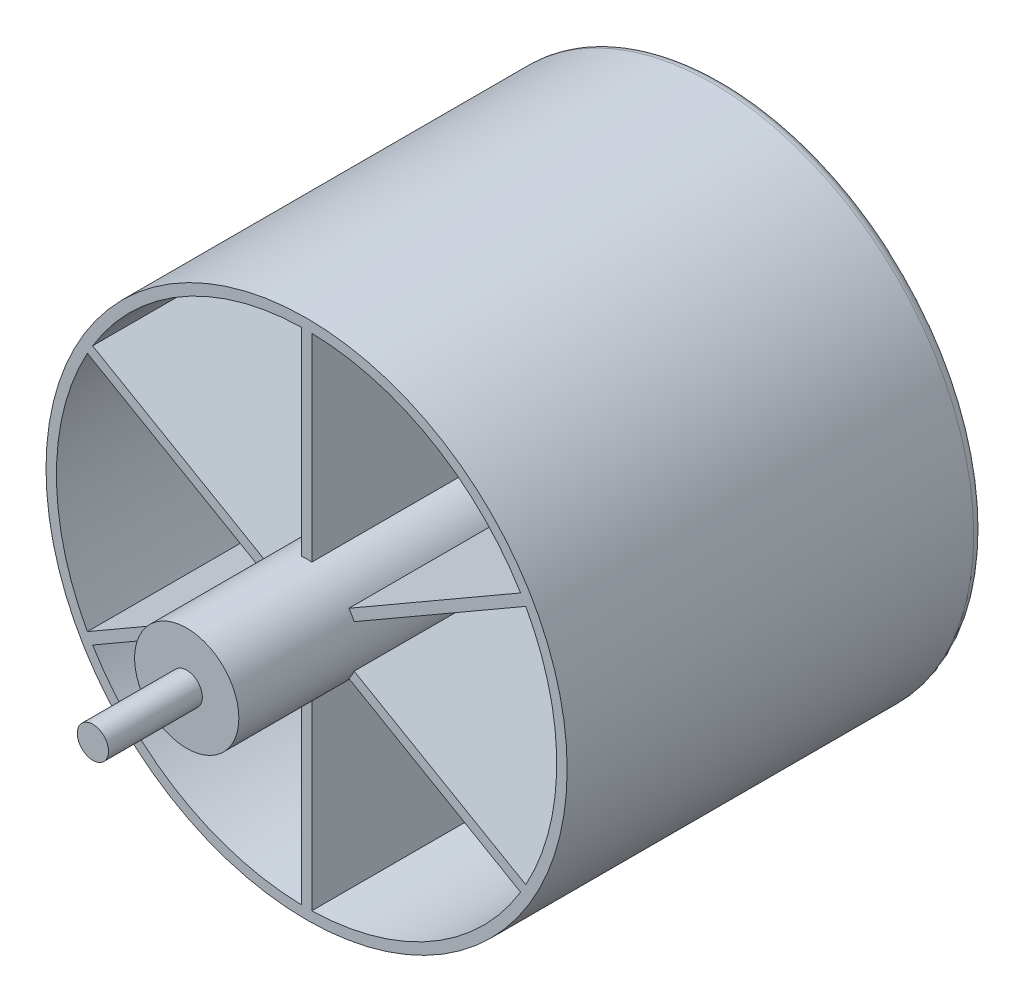
SolidWorks part; units mm, degrees
material "玻璃"
ref_plane "前视基准面" through (0, 0, 0) normal (0, 0, 1) x (1, 0, 0)
ref_plane "上视基准面" through (0, 0, 0) normal (0, 1, 0) x (1, 0, 0)
ref_plane "右视基准面" through (0, 0, 0) normal (1, 0, 0) x (0, 0, -1)
other "Configuration Table"
sketch "草图1" plane through (0, 0, 0) normal (0, 0, 1) x (1, 0, 0)
  circle A0 centre (0, 0) radius 50
  dimension "D1" = 100
extrude "凸台-拉伸1" add sketch "草图1" along normal blind 80
shell "抽壳1" thickness 2 removed face at (50, 0, 80)
sketch "草图2" plane through (0, 0, 2) normal (0, 0, 1) x (1, 0, 0)
  line L0 (0, -1000) -> (0, 49000) construction
  line L1 (-1, 9.9499) -> (-1, 47.9896)
  line L2 (1, 9.9499) -> (1, 47.9896)
  line L3 (8.1168, 5.841) -> (41.0602, 24.8608)
  line L4 (9.1168, 4.1089) -> (42.0602, 23.1288)
  line L5 (9.1168, -4.1089) -> (42.0602, -23.1288)
  line L6 (8.1168, -5.841) -> (41.0602, -24.8608)
  line L7 (1, -9.9499) -> (1, -47.9896)
  line L8 (-1, -9.9499) -> (-1, -47.9896)
  line L9 (-8.1168, -5.841) -> (-41.0602, -24.8608)
  line L10 (-9.1168, -4.1089) -> (-42.0602, -23.1288)
  line L11 (-9.1168, 4.1089) -> (-42.0602, 23.1288)
  line L12 (-8.1168, 5.841) -> (-41.0602, 24.8608)
  circle A0 centre (0, 0) radius 48 construction
  arc A1 (-41.0602, 24.8608) -> (-42.0602, 23.1288) centre (0, 0) ccw
  arc A2 (-9.1168, 4.1089) -> (-9.1168, -4.1089) centre (0, 0) ccw
  arc A3 (1, 47.9896) -> (-1, 47.9896) centre (0, 0) ccw
  arc A4 (42.0602, 23.1288) -> (41.0602, 24.8608) centre (0, 0) ccw
  arc A5 (41.0602, -24.8608) -> (42.0602, -23.1288) centre (0, 0) ccw
  arc A6 (-1, -47.9896) -> (1, -47.9896) centre (0, 0) ccw
  arc A7 (-42.0602, -23.1288) -> (-41.0602, -24.8608) centre (0, 0) ccw
  circle A8 centre (0, 0) radius 8
  arc A9 (-1, 9.9499) -> (-8.1168, 5.841) centre (0, 0) ccw
  arc A10 (8.1168, 5.841) -> (1, 9.9499) centre (0, 0) ccw
  arc A11 (9.1168, -4.1089) -> (9.1168, 4.1089) centre (0, 0) ccw
  arc A12 (-8.1168, -5.841) -> (-1, -9.9499) centre (0, 0) ccw
  arc A13 (1, -9.9499) -> (8.1168, -5.841) centre (0, 0) ccw
  point P32 (0, 0)
  dimension "D1" = 20
  dimension "D4" = 2
  dimension "D2" = 2
  dimension "D3" = 6
extrude "凸台-拉伸2" add sketch "草图2" along normal up to surface (78 mm away) up to face at (48, 0, 80)
sketch "草图3" plane through (0, 0, 2) normal (0, 0, 1) x (1, 0, 0)
  line L0 (0, -1000) -> (0, 49000) construction
  line L1 (0, 0) -> (-25000, 43301.2702) construction
  line L14 (-16.1245, 16.1245) -> (-26.0768, 26.0768)
  line L15 (-5.902, 22.0265) -> (-9.5448, 35.6216)
  line L16 (16.1245, 16.1245) -> (26.0768, 26.0768)
  line L17 (5.902, 22.0265) -> (9.5448, 35.6216)
  line L18 (22.0265, -5.902) -> (35.6216, -9.5448)
  line L19 (22.0265, 5.902) -> (35.6216, 9.5448)
  line L20 (5.902, -22.0265) -> (9.5448, -35.6216)
  line L21 (16.1245, -16.1245) -> (26.0768, -26.0768)
  line L22 (-16.1245, -16.1245) -> (-26.0768, -26.0768)
  line L23 (-5.902, -22.0265) -> (-9.5448, -35.6216)
  line L24 (-22.0265, 5.902) -> (-35.6216, 9.5448)
  line L25 (-22.0265, -5.902) -> (-35.6216, -9.5448)
  line L26 (0, 0) -> (-5.1764, 19.3185) construction
  line L27 (0, 0) -> (14.1421, 14.1421) construction
  arc A36 (-39.3492, 7.1859) -> (-39.3492, -7.1859) centre (0, 0) ccw
  arc A37 (-19.8287, 2.6124) -> (-19.8287, -2.6124) centre (0, 0) ccw
  arc A38 (-7.652, 18.4783) -> (-12.1767, 15.8659) centre (0, 0) ccw
  arc A39 (-13.4514, 37.6704) -> (-25.8978, 30.4845) centre (0, 0) ccw
  arc A40 (25.8978, 30.4845) -> (13.4514, 37.6704) centre (0, 0) ccw
  arc A41 (12.1767, 15.8659) -> (7.652, 18.4783) centre (0, 0) ccw
  arc A42 (19.8287, -2.6124) -> (19.8287, 2.6124) centre (0, 0) ccw
  arc A43 (39.3492, -7.1859) -> (39.3492, 7.1859) centre (0, 0) ccw
  arc A44 (7.652, -18.4783) -> (12.1767, -15.8659) centre (0, 0) ccw
  arc A45 (13.4514, -37.6704) -> (25.8978, -30.4845) centre (0, 0) ccw
  arc A46 (-25.8978, -30.4845) -> (-13.4514, -37.6704) centre (0, 0) ccw
  arc A47 (-12.1767, -15.8659) -> (-7.652, -18.4783) centre (0, 0) ccw
  arc A48 (-22.0265, -5.902) -> (-19.8287, -2.6124) centre (-22.803, -3.0042) ccw
  arc A49 (-22.0265, 5.902) -> (-19.8287, 2.6124) centre (-22.803, 3.0042) cw
  arc A50 (-35.6216, 9.5448) -> (-39.3492, 7.1859) centre (-36.398, 6.647) ccw
  arc A51 (-35.6216, -9.5448) -> (-39.3492, -7.1859) centre (-36.398, -6.647) cw
  arc A52 (-5.902, -22.0265) -> (-7.652, -18.4783) centre (-8.7998, -21.25) ccw
  arc A53 (-16.1245, -16.1245) -> (-12.1767, -15.8659) centre (-14.0032, -18.2458) cw
  arc A54 (-26.0768, -26.0768) -> (-25.8978, -30.4845) centre (-23.9555, -28.1981) ccw
  arc A55 (-9.5448, -35.6216) -> (-13.4514, -37.6704) centre (-12.4426, -34.8451) cw
  arc A56 (26.0768, -26.0768) -> (25.8978, -30.4845) centre (23.9555, -28.1981) cw
  arc A57 (9.5448, -35.6216) -> (13.4514, -37.6704) centre (12.4426, -34.8451) ccw
  arc A58 (5.902, -22.0265) -> (7.652, -18.4783) centre (8.7998, -21.25) cw
  arc A59 (16.1245, -16.1245) -> (12.1767, -15.8659) centre (14.0032, -18.2458) ccw
  arc A60 (35.6216, -9.5448) -> (39.3492, -7.1859) centre (36.398, -6.647) ccw
  arc A61 (35.6216, 9.5448) -> (39.3492, 7.1859) centre (36.398, 6.647) cw
  arc A62 (22.0265, -5.902) -> (19.8287, -2.6124) centre (22.803, -3.0042) cw
  arc A63 (22.0265, 5.902) -> (19.8287, 2.6124) centre (22.803, 3.0042) ccw
  arc A64 (5.902, 22.0265) -> (7.652, 18.4783) centre (8.7998, 21.25) ccw
  arc A65 (16.1245, 16.1245) -> (12.1767, 15.8659) centre (14.0032, 18.2458) cw
  arc A66 (26.0768, 26.0768) -> (25.8978, 30.4845) centre (23.9555, 28.1981) ccw
  arc A67 (9.5448, 35.6216) -> (13.4514, 37.6704) centre (12.4426, 34.8451) cw
  arc A68 (-9.5448, 35.6216) -> (-13.4514, 37.6704) centre (-12.4426, 34.8451) ccw
  arc A69 (-26.0768, 26.0768) -> (-25.8978, 30.4845) centre (-23.9555, 28.1981) cw
  arc A70 (-5.902, 22.0265) -> (-7.652, 18.4783) centre (-8.7998, 21.25) cw
  arc A71 (-16.1245, 16.1245) -> (-12.1767, 15.8659) centre (-14.0032, 18.2458) ccw
  point P75 (-10.3528, 38.637)
  point P78 (-28.2843, 28.2843)
  dimension "D1" = 80
  dimension "D2" = 40
  dimension "D6" = 60
  dimension "D7" = 3
  dimension "D3" = 30
  dimension "D4" = 15
  dimension "D5" = 6
extrude "切除-拉伸1" cut sketch "草图3" against normal blind 150
sketch "草图4" plane through (0, 0, 80) normal (0, 0, 1) x (1, 0, 0)
  circle A0 centre (0, 0) radius 7.5
  circle A1 centre (0, 0) radius 5
  dimension "D1" = 10
  dimension "D2" = 15
extrude "凸台-拉伸3" add sketch "草图4" against normal blind 5 from offset 5 offset against normal yes
sketch "草图5" plane through (0, 0, 2) normal (0, 0, 1) x (1, 0, 0)
  circle A1 centre (0, 0) radius 8
  circle A2 centre (0, 0) radius 8
  dimension "D1" = 0
extrude "切除-拉伸2" cut sketch "草图5" against normal blind 5
sketch "草图6" plane through (0, 0, 0) normal (0, 0, -1) x (-1, 0, 0)
  circle A0 centre (0, 0) radius 7.5
  circle A1 centre (0, 0) radius 5
  dimension "D1" = 15
extrude "凸台-拉伸5" add sketch "草图6" against normal blind 5 from offset 5 offset against normal yes
fillet "圆角1" radius 2 73 edges at (1, -28.9697, 2) (5, -8.6603, 2) (24.5885, -15.3509, 2) (24, -41.5692, 2) (21.1007, -21.1007, 2) (14.1993, -15.2523, 2) (10, -17.3205, 2) (6.1092, -19.9231, 2) (7.7234, -28.824, 2) (11.0492, -37.5019, 2) (20, -34.641, 2) (26.953, -28.3199, 2) (25.5885, -13.6188, 2) (10, 0, 2) (25.5885, 13.6188, 2) (48, 0, 2) (40, 0, 2) (38.0022, 9.1821, 2) (28.824, 7.7234, 2) (20.3085, 4.6708, 2) (20, 0, 2) (20.3085, -4.6708, 2) (28.824, -7.7234, 2) (38.0022, -9.1821, 2) (24.5885, 15.3509, 2) (5, 8.6603, 2) (1, 28.9697, 2) (24, 41.5692, 2) (10, 17.3205, 2) (14.1993, 15.2523, 2) (21.1007, 21.1007, 2) (26.953, 28.3199, 2) (20, 34.641, 2) (11.0492, 37.5019, 2) (7.7234, 28.824, 2) (6.1092, 19.9231, 2) (-24.5885, 15.3509, 2) (-24, 41.5692, 2) (-1, 28.9697, 2) (-5, 8.6603, 2) (-20, 34.641, 2) (-26.953, 28.3199, 2) (-21.1007, 21.1007, 2) (-14.1993, 15.2523, 2) (-10, 17.3205, 2) (-6.1092, 19.9231, 2) (-7.7234, 28.824, 2) (-11.0492, 37.5019, 2) (-24.5885, -15.3509, 2) (-5, -8.6603, 2) (-1, -28.9697, 2) (-24, -41.5692, 2) (-10, -17.3205, 2) (-14.1993, -15.2523, 2) (-21.1007, -21.1007, 2) (-26.953, -28.3199, 2) (-20, -34.641, 2) (-11.0492, -37.5019, 2) (-7.7234, -28.824, 2) (-6.1092, -19.9231, 2) (-25.5885, 13.6188, 2) (-10, 0, 2) (-25.5885, -13.6188, 2) (-48, 0, 2) (-20, 0, 2) (-20.3085, 4.6708, 2) (-28.824, 7.7234, 2) (-38.0022, 9.1821, 2) (-40, 0, 2) (-38.0022, -9.1821, 2) (-28.824, -7.7234, 2) (-20.3085, -4.6708, 2) (50, 0, 0)
sketch "草图7" plane through (0, 0, 0) normal (0, 1, 0) x (1, 0, 0)
  line L0 (0, -1000) -> (0, 49000) construction
  line L1 (8, 0) -> (-8, 0) construction
  line L2 (-10, -80) -> (-10, -101)
  line L4 (-50, -80) -> (50, -80) construction
  line L5 (-8, -80) -> (-8, -101)
  line L6 (-13.4514, 0) -> (-25.8978, 0) construction
  line L7 (-10, -80) -> (-8, -80)
  line L9 (-8, -101) -> (0, -101)
  line L10 (0, -101) -> (0, -121)
  line L11 (0, -121) -> (-3, -121)
  line L12 (-3, -121) -> (-3, -103)
  line L13 (-3, -103) -> (-10, -103)
  line L14 (-10, -103) -> (-10, -101)
  point P5 (0, 0)
  point P16 (0, 0)
  point P22 (0, 0)
  dimension "D1" = 2
  dimension "D2" = 101
  dimension "D3" = 2
  dimension "D4" = 6
  dimension "D5" = 20
  dimension "D6" = 16
revolve "旋转1" add sketch "草图7" angle 360 about L0
